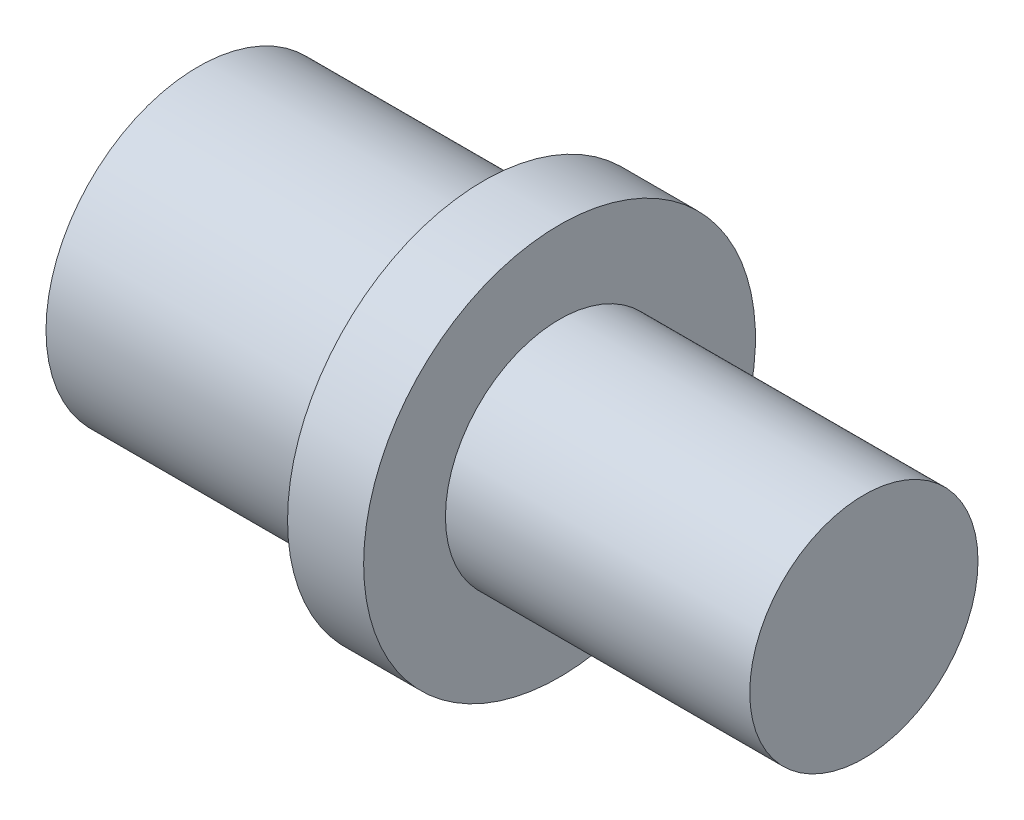
SolidWorks part; units mm, degrees
ref_plane "Front Plane" through (0, 0, 0) normal (0, 0, 1) x (1, 0, 0)
ref_plane "Top Plane" through (0, 0, 0) normal (0, 1, 0) x (1, 0, 0)
ref_plane "Right Plane" through (0, 0, 0) normal (1, 0, 0) x (0, 0, -1)
ref_plane "Plane1" through (-9.5, 0, 0) normal (1, 0, 0) x (0, 0, -1)
sketch "Sketch1" plane through (0, 0, 0) normal (0, 0, 1) x (1, 0, 0)
  line L0 (-9.5, 0) -> (8, 0)
  line L1 (8, 0) -> (8, 3)
  line L2 (8, 3) -> (0, 3)
  line L3 (0, 3) -> (0, 5.15)
  line L4 (0, 5.15) -> (-2, 5.15)
  line L5 (-2, 5.15) -> (-2, 4)
  line L6 (-2, 4) -> (-9.5, 4)
  line L7 (-9.5, 3.2) -> (-9.5, 0)
  line L8 (-9.1905, 0) -> (10.1274, 0) construction
  line L9 (-1, 5.15) -> (-1, 0) construction
  line L10 (-9.5, 4) -> (-9, 3.2)
  line L11 (-9, 3.2) -> (-9.5, 3.2)
  dimension "M" = 6
  dimension "L" = 8
  dimension "L_s" = 1
  dimension "MSM_29" = 1
  dimension "MSM_23" = 10.3
  dimension "D_s" = 8
  dimension "MSM_21" = 7.5
  dimension "FIX_1" = 0.5
  dimension "MSM_22" = 6.4
revolve "Revolve1" add sketch "Sketch1" angle 360 about L8
cosmetic thread "Thread1" parameters "ATD_1"=4.917
sketch "Sketch2" plane through (0, 0, 0) normal (0, 1, 0) x (1, 0, 0)
  line L0 (-9.5, -1.75) -> (-9.5, 1.75) construction
  line L1 (-2, -1.75) -> (-2, 1.75) construction
  line L2 (-1, -1.75) -> (-1, 1.75) construction
  line L3 (0, 1.75) -> (0, -1.75) construction
  line L4 (-8.8, -1.75) -> (-8.8, 1.75) construction
  line L5 (-9.3, -1.75) -> (-9.5, -1.75)
  line L6 (-9.5, -1.75) -> (-9.5, 1.75)
  line L7 (-9.5, 1.75) -> (-9.3, 1.75)
  line L8 (0, 0) -> (-9.5, 0) construction
  line L9 (-8.8, 0.3) -> (-8.8, -0.3)
  arc A0 (-8.8, -0.3) -> (-9.3, -1.75) centre (-11.1525, -0.3) cw
  arc A1 (-8.8, 0.3) -> (-9.3, 1.75) centre (-11.1525, 0.3) ccw
  dimension "L_s" = 1
  dimension "MSM_29" = 1
  dimension "MSM_21" = 7.5
  dimension "MSM_26" = 0.6
  dimension "MSM_24" = 0.7
  dimension "MSM_25" = 3.5
  dimension "MSM_27" = 0.2
extrude "Cut-Extrude1" [suppressed] cut sketch "Sketch2" against normal mid plane 0.6
sketch "Sketch3" plane through (0, 0, 0) normal (0, 0, -1) x (0, 1, 0)
  line L0 (1.75, -9.5) -> (-1.75, -9.5) construction
  line L1 (1.75, -2) -> (-1.75, -2) construction
  line L2 (1.75, -1) -> (-1.75, -1) construction
  line L3 (-1.75, 0) -> (1.75, 0) construction
  line L4 (1.75, -8.8) -> (-1.75, -8.8) construction
  line L5 (1.75, -9.3) -> (1.75, -9.5)
  line L6 (1.75, -9.5) -> (-1.75, -9.5)
  line L7 (-1.75, -9.5) -> (-1.75, -9.3)
  line L8 (0, 0) -> (0, -9.5) construction
  line L9 (-0.3, -8.8) -> (0.3, -8.8)
  arc A0 (0.3, -8.8) -> (1.75, -9.3) centre (0.3, -11.1525) cw
  arc A1 (-0.3, -8.8) -> (-1.75, -9.3) centre (-0.3, -11.1525) ccw
  dimension "L_s" = 1
  dimension "MSM_29" = 1
  dimension "MSM_21" = 7.5
  dimension "MSM_26" = 0.6
  dimension "MSM_24" = 0.7
  dimension "MSM_25" = 3.5
  dimension "MSM_27" = 0.2
extrude "Cut-Extrude2" [suppressed] cut sketch "Sketch3" against normal mid plane 0.6
sketch "Sketch4" plane through (-9.5, 0, 0) normal (1, 0, 0) x (0, 0, -1)
  line L1 (0, 2.8868) -> (-2.5, 1.4434)
  line L2 (-2.5, 1.4434) -> (-2.5, -1.4434)
  line L3 (-2.5, -1.4434) -> (0, -2.8868)
  line L4 (0, -2.8868) -> (2.5, -1.4434)
  line L5 (2.5, -1.4434) -> (2.5, 1.4434)
  line L6 (2.5, 1.4434) -> (0, 2.8868)
  circle A0 centre (0, 0) radius 2.5 construction
  dimension "G" = 5
sketch "Sketch5" plane through (0, 0, 0) normal (0, 0, 1) x (1, 0, 0)
  line L0 (-9.5, 2.5) -> (-7, 2.5)
  line L2 (-7, 2.5) -> (-5.4978, 0)
  line L3 (-5.4978, 0) -> (-9.5, 0)
  line L4 (-9.5, 0) -> (-9.5, 2.5)
  line L5 (-5.4978, 0) -> (-7, -2.5) construction
  line L6 (-9.5, 0) -> (0, 0) construction
  dimension "KSS_1" = 9.5
  dimension "FIX_4" = 118
  dimension "G" = 5
  dimension "MSM_28" = 2.5
revolve "Cut-Revolve1" cut sketch "Sketch5" angle 360 about L6
extrude "Cut-Extrude3" cut sketch "Sketch4" along normal blind 2.5
equation "\"KSS_1@Plane1\"= \"MSM_29@Sketch1\" + \"L_s@Sketch1\" + \"MSM_21@Sketch1\""
equation "\"KSS_1@Sketch5\"= \"MSM_29@Sketch1\" + \"L_s@Sketch1\" + \"MSM_21@Sketch1\""
